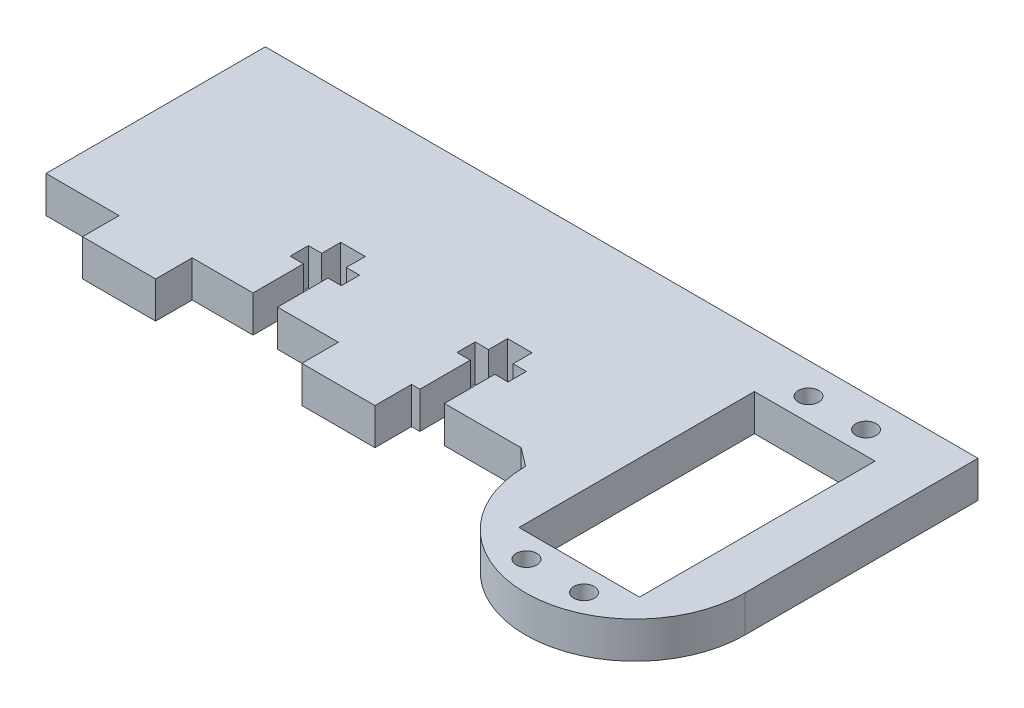
SolidWorks part; units mm, degrees
ref_plane "Front Plane" through (0, 0, 0) normal (0, 0, 1) x (1, 0, 0)
ref_plane "Top Plane" through (0, 0, 0) normal (0, 1, 0) x (1, 0, 0)
ref_plane "Right Plane" through (0, 0, 0) normal (1, 0, 0) x (0, 0, -1)
sketch "Sketch1" plane through (0, 0, 0) normal (0, 1, 0) x (1, 0, 0)
  line L0 (64.8104, 44.2474) -> (64.8104, -38.3026)
  line L1 (-62.1896, 44.2474) -> (64.8104, 44.2474)
  line L2 (-62.1896, 44.2474) -> (-62.1896, -12.9026)
  line L3 (-62.1896, -12.9026) -> (-49.4896, -12.9026)
  line L4 (-36.7896, -12.9026) -> (-11.3896, -12.9026)
  line L6 (1.3104, -12.9026) -> (1.3104, -19.2526)
  line L7 (64.8104, -38.3026) -> (20.3604, -38.3026)
  line L8 (20.3604, -12.9026) -> (20.3604, -38.3026)
  line L9 (1.3104, -19.2526) -> (-11.3896, -19.2526)
  line L10 (-11.3896, -12.9026) -> (-11.3896, -19.2526)
  line L11 (1.3104, -12.9026) -> (20.3604, -12.9026)
  line L12 (-36.7896, -12.9026) -> (-36.7896, -19.2526)
  line L13 (-36.7896, -19.2526) -> (-49.4896, -19.2526)
  line L14 (-49.4896, -12.9026) -> (-49.4896, -19.2526)
  dimension "D1" = 25.4
  dimension "D2" = 57.15
  dimension "D3" = 6.35
  dimension "D4" = 6.35
  dimension "D5" = 12.7
  dimension "D6" = 12.7
  dimension "D7" = 25.4
  dimension "D8" = 19.05
  dimension "D9" = 44.45
  dimension "D10" = 12.7
extrude "Boss-Extrude1" add sketch "Sketch1" along normal blind 6.35
sketch "Sketch2" plane through (0, 0, 0) normal (0, -1, 0) x (1, 0, 0)
  line L0 (20.3604, 12.9026) -> (23.5354, 15.3055)
  line L1 (61.6354, 15.3055) -> (61.6354, -44.2474)
  line L2 (64.8104, -44.2474) -> (-62.1896, -44.2474) construction
  line L3 (61.6354, -44.2474) -> (64.8104, -44.2474)
  line L4 (64.8104, -44.2474) -> (64.8104, 38.3026)
  line L5 (64.8104, 38.3026) -> (64.8104, -44.2474) construction
  line L6 (64.8104, 38.3026) -> (20.3604, 38.3026)
  line L7 (20.3604, 38.3026) -> (20.3604, 12.9026)
  arc A0 (61.6354, 15.3055) -> (23.5354, 15.3055) centre (42.5854, 15.3055) ccw
extrude "Cut-Extrude1" cut sketch "Sketch2" against normal through all
sketch "Sketch4" plane through (0, 0, 0) normal (0, -1, 0) x (1, 0, 0)
  line L1 (32.1671, 25.0919) -> (53.1176, 25.0919)
  line L2 (32.1671, 25.0919) -> (32.1671, -15.8271)
  line L3 (32.1671, -15.8271) -> (53.1176, -15.8271)
  line L4 (53.1176, 25.0919) -> (53.1176, -15.8271)
extrude "Cut-Extrude2" cut sketch "Sketch4" against normal through all
sketch "Sketch5" plane through (0, 6.35, 0) normal (0, 1, 0) x (1, 0, 0)
  line L0 (-62.1896, 44.2474) -> (-62.1896, -12.9026) construction
  line L1 (61.6354, 44.2474) -> (-62.1896, 44.2474)
  line L2 (61.6354, 44.2474) -> (61.6354, 25.1974)
  line L3 (61.6354, 25.1974) -> (-62.1896, 25.1974)
  line L4 (-62.1896, 44.2474) -> (-62.1896, 25.1974)
  circle A0 centre (47.5854, -29.201) radius 1.778
  circle A1 centre (37.5854, -29.201) radius 1.778
  circle A2 centre (47.5854, 19.799) radius 1.778
  circle A3 centre (37.5854, 19.799) radius 1.778
  dimension "D1" = 19.05
extrude "Cut-Extrude3" cut sketch "Sketch5" against normal through all
sketch "Sketch6" plane through (0, 6.35, 0) normal (0, 1, 0) x (1, 0, 0)
  line L1 (-36.7896, -12.9026) -> (-11.3896, -12.9026) construction
  line L2 (-24.0896, -12.9026) -> (-24.0896, 2.4668) construction
  line B0 (2.759, -12.9026) -> (7.0262, -12.9026)
  line B1 (7.0262, -0.9646) -> (9.3376, -0.9646)
  line B2 (9.3376, -0.9646) -> (9.3376, -4.1396)
  line B3 (9.3376, -4.1396) -> (7.0262, -4.1396)
  line B4 (7.0262, -4.1396) -> (7.0262, -12.9026)
  line B5 (7.0262, -0.9646) -> (7.0262, 2.3374)
  line B6 (7.0262, 2.3374) -> (2.759, 2.3374)
  line B7 (2.759, -0.9646) -> (2.759, 2.3374)
  line B8 (2.759, -4.1396) -> (2.759, -12.9026)
  line B9 (0.4476, -4.1396) -> (2.759, -4.1396)
  line B10 (0.4476, -0.9646) -> (0.4476, -4.1396)
  line B11 (2.759, -0.9646) -> (0.4476, -0.9646)
  line B12 (-26.2232, -12.9026) -> (-21.956, -12.9026)
  line B13 (-21.956, -0.9646) -> (-19.6446, -0.9646)
  line B14 (-19.6446, -0.9646) -> (-19.6446, -4.1396)
  line B15 (-19.6446, -4.1396) -> (-21.956, -4.1396)
  line B16 (-21.956, -4.1396) -> (-21.956, -12.9026)
  line B17 (-21.956, -0.9646) -> (-21.956, 2.3374)
  line B18 (-21.956, 2.3374) -> (-26.2232, 2.3374)
  line B19 (-26.2232, -0.9646) -> (-26.2232, 2.3374)
  line B20 (-26.2232, -4.1396) -> (-26.2232, -12.9026)
  line B21 (-28.5346, -4.1396) -> (-26.2232, -4.1396)
  line B22 (-28.5346, -0.9646) -> (-28.5346, -4.1396)
  line B23 (-26.2232, -0.9646) -> (-28.5346, -0.9646)
sketch_block_instance "TSlot-1"
sketch_block "TSlot" parameters "D1"=3.302, "D2"=3.175
sketch_block_instance "TSlot-3"
extrude "Cut-Extrude4" cut sketch "Sketch6" against normal through all
